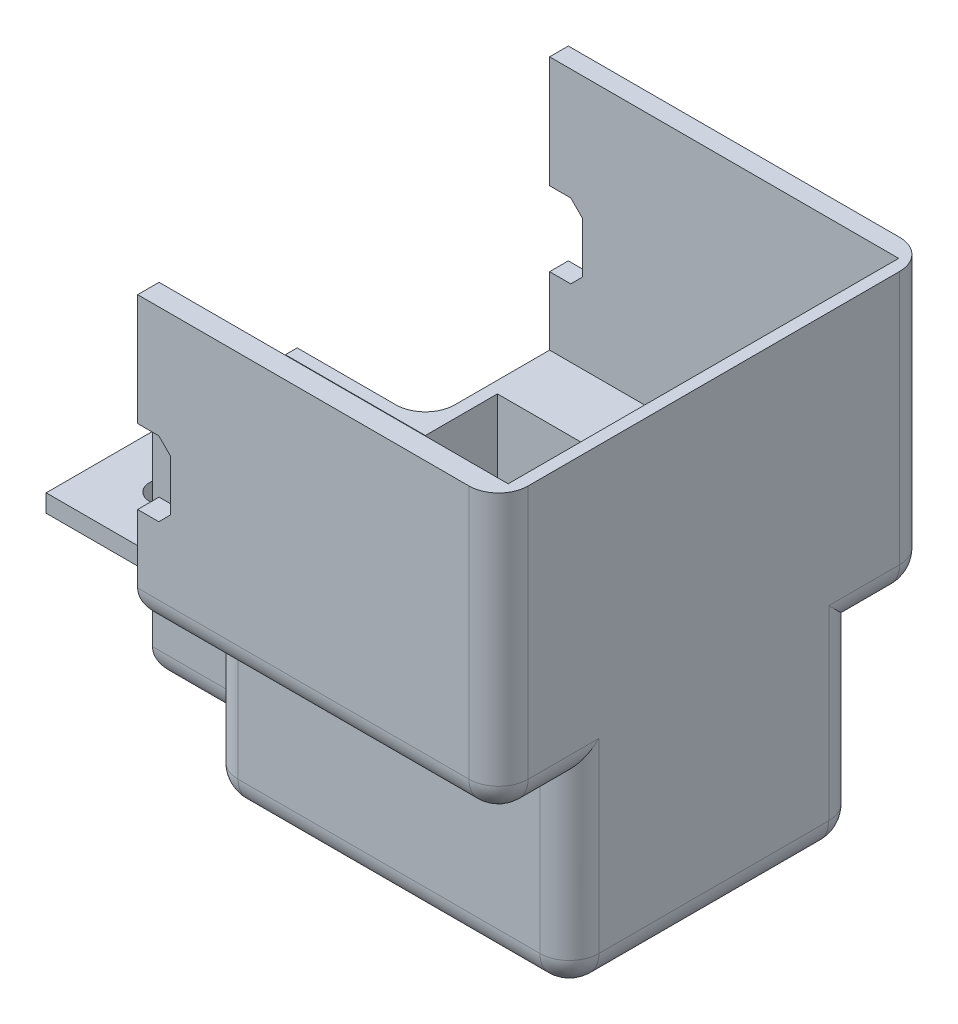
SolidWorks part; units mm, degrees
material "ABS"
ref_plane "Front Plane" through (0, 0, 0) normal (0, 0, 1) x (1, 0, 0)
ref_plane "Top Plane" through (0, 0, 0) normal (0, 1, 0) x (1, 0, 0)
ref_plane "Right Plane" through (0, 0, 0) normal (1, 0, 0) x (0, 0, -1)
sketch "Sketch1" plane through (0, 0, 0) normal (0, 1, 0) x (1, 0, 0)
  line L1 (-30.5479, -24.4551) -> (30.5479, -24.4551)
  line L2 (-30.5479, -24.4551) -> (-30.5479, 24.4551)
  line L3 (-30.5479, 24.4551) -> (30.5479, 24.4551)
  line L4 (30.5479, -24.4551) -> (30.5479, 24.4551)
  line L5 (-30.5479, -24.4551) -> (30.5479, 24.4551) construction
  line L6 (-30.5479, 24.4551) -> (30.5479, -24.4551) construction
  line L7 (-8.8548, -12.25) -> (-52.241, -12.25)
  line L8 (-8.8548, -12.25) -> (-8.8548, 12.25)
  line L9 (-8.8548, 12.25) -> (-52.241, 12.25)
  line L10 (-52.241, -12.25) -> (-52.241, 12.25)
  line L11 (-8.8548, -12.25) -> (-52.241, 12.25) construction
  line L12 (-8.8548, 12.25) -> (-52.241, -12.25) construction
  point P0 (0, 0)
  point P6 (-30.5479, 0)
  dimension "D1" = 24.5
extrude "Boss-Extrude1" add sketch "Sketch1" along normal blind 2.54 contours L9 L8 L7 L2 L1 L4 L3 | L10 L7 L2 L9 | L8 L9 L2 L7 region at (4.2621, 0, 0) region at (-41.3944, 0, 0) region at (-19.7013, 0, 0)
sketch "Sketch2" plane through (0, 2.54, 0) normal (0, 1, 0) x (1, 0, 0)
  line L0 (28.5479, 22.4551) -> (-28.5479, 22.4551)
  line L1 (-28.5479, 22.4551) -> (-28.5479, 10.25)
  line L2 (-28.5479, 10.25) -> (-50.241, 10.25)
  line L3 (-50.241, 10.25) -> (-50.241, -10.25)
  line L4 (-50.241, -10.25) -> (-28.5479, -10.25)
  line L5 (-28.5479, -10.25) -> (-28.5479, -22.4551)
  line L6 (-28.5479, -22.4551) -> (28.5479, -22.4551)
  line L7 (28.5479, -22.4551) -> (28.5479, 22.4551)
  line L8 (-30.5479, 24.4551) -> (-30.5479, 12.25)
  line L9 (-30.5479, 12.25) -> (-52.241, 12.25)
  line L10 (-52.241, 12.25) -> (-52.241, -12.25)
  line L11 (-52.241, -12.25) -> (-30.5479, -12.25)
  line L12 (-30.5479, -12.25) -> (-30.5479, -24.4551)
  line L13 (-30.5479, -24.4551) -> (30.5479, -24.4551)
  line L14 (30.5479, -24.4551) -> (30.5479, 24.4551)
  line L15 (30.5479, 24.4551) -> (-30.5479, 24.4551)
  line L16 (-30.5479, 24.4551) -> (-30.5479, 12.25)
  line L17 (-30.5479, 12.25) -> (-52.241, 12.25)
  line L18 (-52.241, 12.25) -> (-52.241, -12.25)
  line L19 (-52.241, -12.25) -> (-30.5479, -12.25)
  line L20 (-30.5479, -12.25) -> (-30.5479, -24.4551)
  line L21 (-30.5479, -24.4551) -> (30.5479, -24.4551)
  line L22 (30.5479, -24.4551) -> (30.5479, 24.4551)
  line L23 (30.5479, 24.4551) -> (-30.5479, 24.4551)
  dimension "D1" = 0
  dimension "D2" = 2
extrude "Boss-Extrude2" add sketch "Sketch2" along normal blind 34
sketch "Sketch3" plane through (0, 2.54, 0) normal (0, 1, 0) x (1, 0, 0)
  line L0 (-49.2072, 10.25) -> (-55.7179, 10.25)
  line L1 (-28.5479, 10.25) -> (-50.241, 10.25) construction
  line L2 (-48.4153, -10.25) -> (-55.7179, -10.25)
  line L3 (-50.241, -10.25) -> (-28.5479, -10.25) construction
  line L4 (-55.7179, -10.25) -> (-55.7179, 10.25)
  line L5 (-49.2072, 10.25) -> (-48.4153, -10.25)
extrude "Cut-Extrude1" cut sketch "Sketch3" along normal up to surface (34 mm away) up to face at (-20.6972, 36.54, 0)
sketch "Sketch4" plane through (0, 2.54, 0) normal (0, 1, 0) x (1, 0, 0)
  line L0 (-52.241, 10.25) -> (-52.241, -10.25)
  line L1 (-52.241, -10.25) -> (-50.241, -10.25)
  line L2 (-52.241, -10.25) -> (-28.5479, -10.25) construction
  line L3 (-50.241, -10.25) -> (-50.241, 10.25)
  line L4 (-28.5479, 10.25) -> (-52.241, 10.25) construction
  line L5 (-52.241, 10.25) -> (-50.241, 10.25)
  dimension "D1" = 2
extrude "Boss-Extrude3" add sketch "Sketch4" along normal blind 14
sketch "Sketch5" plane through (-52.241, 0, 0) normal (-1, 0, 0) x (0, 0, 1)
  line L1 (10.25, 16.54) -> (-10.25, 16.54)
  line L2 (10.25, 16.54) -> (10.25, 13.54)
  line L3 (10.25, 13.54) -> (-10.25, 13.54)
  line L4 (-10.25, 16.54) -> (-10.25, 13.54)
  dimension "D1" = 3
extrude "Boss-Extrude4" add sketch "Sketch5" along normal blind 20
sketch "Sketch6" plane through (0, 0, -24.4551) normal (0, 0, -1) x (-1, 0, 0)
  line L0 (-30.5479, 36.54) -> (-30.5479, 0) construction
  line L1 (30.5479, 36.54) -> (-30.5479, 36.54)
  line L2 (30.5479, 36.54) -> (30.5479, 31.54)
  line L3 (30.5479, 31.54) -> (-30.5479, 31.54)
  line L4 (-30.5479, 36.54) -> (-30.5479, 31.54)
  dimension "D1" = 5
extrude "Boss-Extrude5" add sketch "Sketch6" along normal blind 12
mirror "Mirror1" about plane through (0, 0, 0) normal (0, 0, 1) of "Boss-Extrude5"
sketch "Sketch7" plane through (0, 36.54, 0) normal (0, 1, 0) x (1, 0, 0)
  line L0 (-30.5479, 33.2831) -> (30.5479, 33.2831)
  line L1 (-30.5479, 36.4551) -> (-30.5479, 12.25) construction
  line L2 (30.5479, -36.4551) -> (30.5479, 36.4551) construction
  line L3 (28.5479, 36.4551) -> (28.5479, -36.4551)
  line L4 (-30.5479, 36.4551) -> (30.5479, 36.4551) construction
  line L5 (-30.5479, -36.4551) -> (30.5479, -36.4551) construction
  line L6 (-30.5479, -32.8318) -> (28.5479, -32.8318)
  line L7 (-30.5479, -12.25) -> (-30.5479, -36.4551) construction
  line L8 (-30.5479, 33.2831) -> (-30.5479, 36.4551)
  line L9 (-30.5479, 36.4551) -> (30.5479, 36.4551)
  line L10 (30.5479, 36.4551) -> (30.5479, -36.4551)
  line L11 (30.5479, -36.4551) -> (-30.5479, -36.4551)
  line L12 (-30.5479, -36.4551) -> (-30.5479, -32.8318)
  line M6 (28.5479, 22.4551) -> (28.5479, -22.4551)
  line M12 (-30.5479, -12.25) -> (-30.5479, -36.4551)
  line M13 (-30.5479, -36.4551) -> (30.5479, -36.4551)
  line M14 (30.5479, -36.4551) -> (30.5479, 36.4551)
  line M15 (30.5479, 36.4551) -> (-30.5479, 36.4551)
  line M16 (-30.5479, 36.4551) -> (-30.5479, 12.25)
extrude "Boss-Extrude6" add sketch "Sketch7" along normal blind 43 contours L3 L0 M15 M16 | L3 L0 M15 M14 | L0 L3 M6 M13 M14 | L6 L3 M12 M13 region at (-1, 36.54, -34.8691) region at (29.5479, 36.54, -34.8691) region at (29.5479, 36.54, 1.586) region at (-1, 36.54, 34.6434)
sketch "Sketch8" plane through (0, 0, -36.4551) normal (0, 0, -1) x (-1, 0, 0)
  line L0 (30.5479, 48.0435) -> (24.9666, 48.0435)
  line L1 (30.5479, 31.54) -> (30.5479, 79.54) construction
  line L2 (32.3466, 51.215) -> (32.3466, 57.465) construction
  line L3 (32.3466, 54.34) -> (24.9666, 54.34) construction
  line L4 (24.9666, 48.0435) -> (24.9666, 60.6365)
  line L5 (30.5479, 48.0435) -> (30.5479, 60.6365)
  line L6 (30.5479, 60.6365) -> (24.9666, 60.6365)
  point P11 (30.5479, 54.34)
extrude "Cut-Extrude2" cut sketch "Sketch8" against normal through all
chamfer "Chamfer1" distance 2 angle 45 4 edges at (-24.9666, 60.6365, -34.8691) (-24.9666, 48.0435, -34.8691) (-24.9666, 60.6365, 34.6434) (-24.9666, 48.0435, 34.6434)
sketch "Sketch9" plane through (0, 13.54, 0) normal (0, -1, 0) x (1, 0, 0)
  line L0 (-62.241, -10.25) -> (-62.241, 10.25) construction
  line L1 (-72.241, -10.25) -> (-52.241, -10.25) construction
  line L2 (-72.241, 10.25) -> (-52.241, 10.25) construction
  circle A0 centre (-62.241, 0) radius 2.75
  dimension "D1" = 5.5
extrude "Cut-Extrude3" cut sketch "Sketch9" against normal blind 43
fillet "Fillet1" radius 5 23 edges at (-30.5479, 0, -18.3525) (-30.5479, 0, 18.3525) (-52.241, 13.54, 0) (-52.241, 0, 0) (-41.3944, 0, -12.25) (-41.3944, 0, 12.25) (-30.5479, 18.27, 12.25) (-30.5479, 18.27, -12.25) (-30.5479, 15.77, 24.4551) (-30.5479, 31.54, 30.4551) (-30.5479, 31.54, -30.4551) (-30.5479, 15.77, -24.4551) (0, 31.54, -36.4551) (30.5479, 31.54, -30.4551) (30.5479, 55.54, -36.4551) (30.5479, 55.54, 36.4551) (30.5479, 31.54, 30.4551) (0, 31.54, 36.4551) (30.5479, 15.77, -24.4551) (30.5479, 15.77, 24.4551) (30.5479, 0, 0) (0, 0, 24.4551) (0, 0, -24.4551)
fillet "Fillet2" radius 5 2 edges at (-52.241, 12.54, -10.25) (-52.241, 12.54, 10.25)
sketch "Sketch10" plane through (0, 0, 0) normal (0, -1, 0) x (1, 0, 0)
  text T0 "Made in Surveyor Inches"
extrude "Cut-Extrude4" cut sketch "Sketch10" against normal blind 0.5
